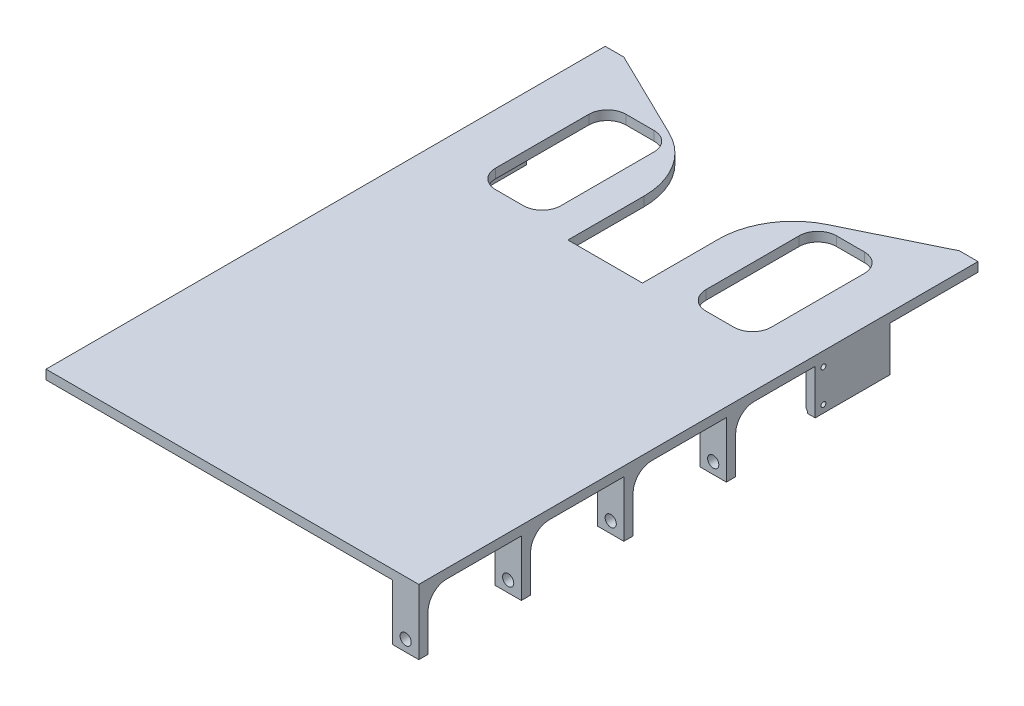
SolidWorks part; units mm, degrees
ref_plane "Front Plane" through (0, 0, 0) normal (0, 0, 1) x (1, 0, 0)
ref_plane "Top Plane" through (0, 0, 0) normal (0, 1, 0) x (1, 0, 0)
ref_plane "Right Plane" through (0, 0, 0) normal (1, 0, 0) x (0, 0, -1)
sketch "Sketch1" plane through (0, 0, 0) normal (0, 1, 0) x (1, 0, 0)
  line L0 (0, 0) -> (0, -300)
  line L1 (0, -300) -> (200, -300)
  line L2 (200, -300) -> (200, 0)
  line L3 (200, 0) -> (190, 0)
  line L4 (190, 0) -> (120, -34.1581)
  line L5 (120, -34.1581) -> (120, -100)
  line L6 (120, -100) -> (80, -100)
  line L7 (80, -100) -> (80, -34.1581)
  line L8 (80, -34.1581) -> (10, 0)
  line L9 (10, 0) -> (0, 0)
  line L10 (100, -300) -> (100, -100) construction
  point P9 (100, -100)
  dimension "D1" = 300
  dimension "D2" = 10
  dimension "D3" = 200
  dimension "D4" = 100
  dimension "D5" = 10
  dimension "D6" = 40
extrude "Boss-Extrude1" add sketch "Sketch1" along normal blind 5
sketch "Sketch2" plane through (0, 0, 0) normal (0, -1, 0) x (1, 0, 0)
  line L0 (0, 0) -> (0, 300) construction
  line L1 (0, 87.3209) -> (5, 87.3209)
  line L2 (0, 87.3209) -> (0, 47.3209)
  line L3 (0, 47.3209) -> (5, 47.3209)
  line L4 (5, 87.3209) -> (5, 47.3209)
  line L5 (200, 300) -> (200, 0) construction
  line L6 (200, 87.3209) -> (195, 87.3209)
  line L7 (200, 87.3209) -> (200, 47.3209)
  line L8 (200, 47.3209) -> (195, 47.3209)
  line L9 (195, 87.3209) -> (195, 47.3209)
  dimension "D1" = 5
  dimension "D2" = 40
  dimension "D3" = 5
extrude "Boss-Extrude2" add sketch "Sketch2" along normal blind 24
sketch "Sketch3" plane through (200, 0, 0) normal (1, 0, 0) x (0, 0, -1)
  line L4 (-47.3209, 0) -> (-87.3209, 0)
  line L5 (-47.3209, -24) -> (-47.3209, 0)
  line L6 (-87.3209, -24) -> (-47.3209, -24)
  line L7 (-87.3209, 0) -> (-87.3209, -24)
  line L8 (-47.3209, 0) -> (-87.3209, 0)
  line L9 (-47.3209, -24) -> (-47.3209, 0)
  line L10 (-87.3209, -24) -> (-47.3209, -24)
  line L11 (-87.3209, 0) -> (-87.3209, -24)
  circle A0 centre (-82.9, -2.5) radius 1.3 construction
  circle A1 centre (-82.9, -20) radius 1.3 construction
  circle A2 centre (-82.9, -2.5) radius 1.3
  circle A3 centre (-82.9, -20) radius 1.3
  dimension "D1" = 0
extrude "Cut-Extrude2" cut sketch "Sketch3" against normal through all contours A3 | A2
sketch "Sketch4" plane through (0, 5, 0) normal (0, 1, 0) x (1, 0, 0)
  line L0 (200, 0) -> (190, 0) construction
  line L1 (175.0541, -26) -> (140.0541, -26)
  line L2 (175.0541, -26) -> (175.0541, -96)
  line L3 (175.0541, -96) -> (140.0541, -96)
  line L4 (140.0541, -26) -> (140.0541, -96)
  line L5 (62.176, -26) -> (27.176, -26)
  line L6 (62.176, -26) -> (62.176, -96)
  line L7 (62.176, -96) -> (27.176, -96)
  line L8 (27.176, -26) -> (27.176, -96)
  dimension "D1" = 35
  dimension "D2" = 35
  dimension "D3" = 26
  dimension "D4" = 70
extrude "Cut-Extrude3" cut sketch "Sketch4" against normal up to next
fillet "Fillet1" radius 10 8 edges at (27.176, 2.5, 26) (27.176, 2.5, 96) (62.176, 2.5, 96) (62.176, 2.5, 26) (140.0541, 2.5, 96) (175.0541, 2.5, 96) (175.0541, 2.5, 26) (140.0541, 2.5, 26)
fillet "Fillet2" radius 40 2 edges at (120, 2.5, 34.1581) (80, 2.5, 34.1581)
sketch "Sketch5" plane through (0, 0, 0) normal (0, -1, 0) x (1, 0, 0)
  line L0 (200, 300) -> (200, 87.3209) construction
  line L1 (200, 295) -> (185.8997, 295)
  line L2 (200, 295) -> (200, 300)
  line L3 (200, 300) -> (185.8997, 300)
  line L4 (185.8997, 295) -> (185.8997, 300)
  line L5 (0, 300) -> (200, 300) construction
  line L6 (200, 240) -> (185.8997, 240)
  line L7 (200, 240) -> (200, 245)
  line L8 (200, 245) -> (185.8997, 245)
  line L9 (185.8997, 240) -> (185.8997, 245)
  line L10 (200, 185) -> (185.8997, 185)
  line L11 (200, 185) -> (200, 190)
  line L12 (200, 190) -> (185.8997, 190)
  line L13 (185.8997, 185) -> (185.8997, 190)
  line L14 (200, 130) -> (185.8997, 130)
  line L15 (200, 130) -> (200, 135)
  line L16 (200, 135) -> (185.8997, 135)
  line L17 (185.8997, 130) -> (185.8997, 135)
  dimension "D1" = 5
  dimension "D2" = 5
  dimension "D3" = 5
  dimension "D4" = 5
  dimension "D5" = 50
  dimension "D6" = 50
  dimension "D7" = 50
extrude "Boss-Extrude3" add sketch "Sketch5" along normal blind 30
fillet "Fillet3" radius 10 4 edges at (192.9498, 0, 130) (192.9498, 0, 185) (192.9498, 0, 240) (192.9498, 0, 295)
sketch "Sketch6" plane through (0, 0, 300) normal (0, 0, 1) x (1, 0, 0)
  line L0 (200, -30) -> (185.8997, -30) construction
  circle A0 centre (192.9498, -24) radius 3
  point P5 (192.9498, -30)
  dimension "D1" = 6
  dimension "D2" = 6
extrude "Cut-Extrude4" cut sketch "Sketch6" against normal through all
